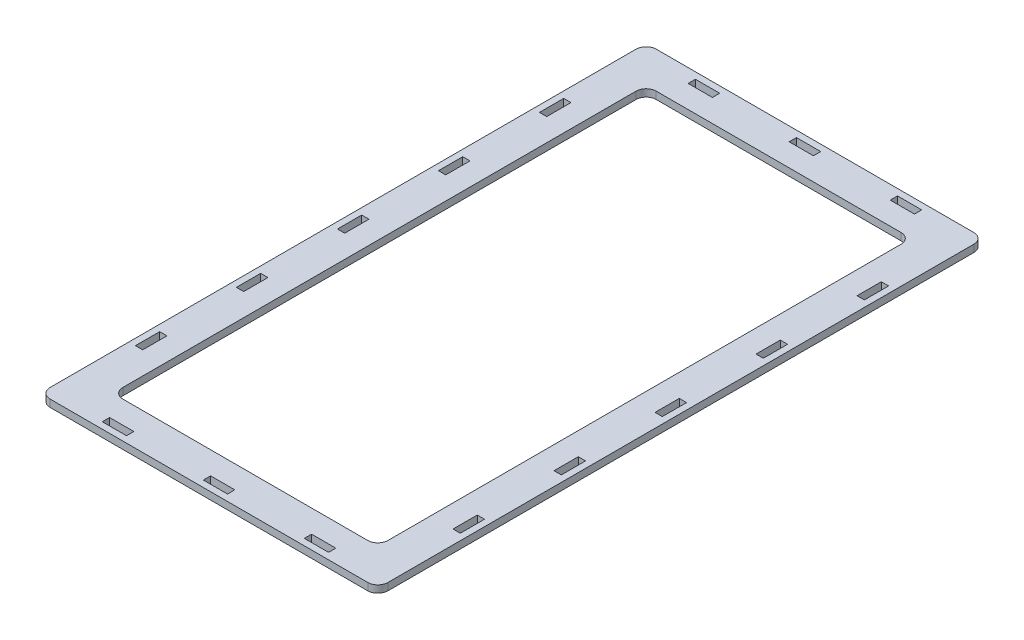
SolidWorks part; units mm, degrees
ref_plane "前视基准面" through (0, 0, 0) normal (0, 0, 1) x (1, 0, 0)
ref_plane "上视基准面" through (0, 0, 0) normal (0, 1, 0) x (1, 0, 0)
ref_plane "右视基准面" through (0, 0, 0) normal (1, 0, 0) x (0, 0, -1)
other "Configuration Table"
sketch "草图1" plane through (0, 0, 0) normal (0, 1, 0) x (1, 0, 0)
  line L1 (-418, 750) -> (418, 750)
  line L2 (-418, 750) -> (-418, -750)
  line L3 (-418, -750) -> (418, -750)
  line L4 (418, 750) -> (418, -750)
  line L5 (-402, -470) -> (-384, -470)
  line L6 (-402, -470) -> (-402, -530)
  line L7 (-402, -530) -> (-384, -530)
  line L8 (-384, -470) -> (-384, -530)
  line L9 (-280, -734) -> (-220, -734)
  line L10 (-280, -734) -> (-280, -716)
  line L11 (-280, -716) -> (-220, -716)
  line L12 (-220, -734) -> (-220, -716)
  line L13 (-328, 660) -> (328, 660)
  line L14 (-328, 660) -> (-328, -660)
  line L15 (-328, -660) -> (328, -660)
  line L16 (328, 660) -> (328, -660)
  point P4 (-418, 0)
  point P6 (0, -750)
  point P11 (-402, -500)
  point P20 (0, -660)
  point P21 (-328, 0)
  point P23 (-220, -725)
  point P24 (-393, -530)
  dimension "D1" = 836
  dimension "D2" = 1500
  dimension "D3" = 250
  dimension "D4" = 18
  dimension "D5" = 60
  dimension "D6" = 90
  dimension "D7" = 90
  dimension "D8" = 60
  dimension "D9" = 18
  dimension "D10" = 138
  dimension "D11" = 25
  dimension "D12" = 25
  dimension "D13" = 16
extrude "凸台-拉伸1" add sketch "草图1" along normal blind 18 contours L2 L3 L4 L1 | L14 L15 L16 L13
extrude "切除-拉伸1" cut sketch "草图1<5>" along normal through all contours L7 L8 L5 L6
sketch "草图1<5>" plane through (0, 0, 0) normal (0, 1, 0) x (1, 0, 0) same geometry as "草图1"
pattern_linear "阵列(线性)1" count 5 spacing 250 along (0, 0, -1) of "切除-拉伸1"
mirror "镜向1" about plane through (0, 0, 0) normal (1, 0, 0) of "切除-拉伸1", "阵列(线性)1"
extrude "切除-拉伸2" cut sketch "草图1<4>" along normal through all contours L12 L11 L10 L9
sketch "草图1<4>" plane through (0, 0, 0) normal (0, 1, 0) x (1, 0, 0) same geometry as "草图1"
pattern_linear "阵列(线性)2" count 3 spacing 250 along (1, 0, 0) of "切除-拉伸2"
mirror "镜向2" about plane through (0, 0, 0) normal (0, 0, 1) of "阵列(线性)2", "切除-拉伸2"
fillet "圆角1" radius 25 4 edges at (-418, 9, -750) (418, 9, -750) (418, 9, 750) (-418, 9, 750)
fillet "圆角2" radius 25 4 edges at (-328, 9, -660) (328, 9, -660) (328, 9, 660) (-328, 9, 660)
